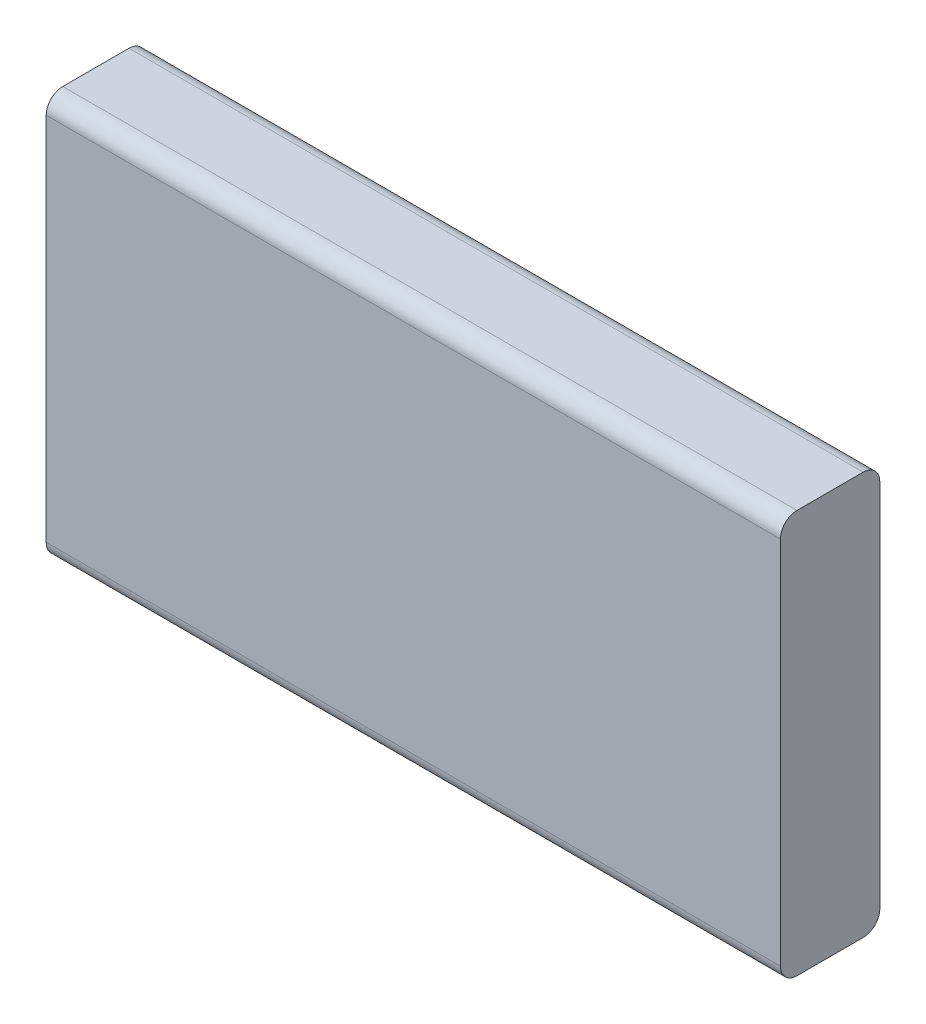
SolidWorks part; units mm, degrees
ref_plane "Plano frontal" through (0, 0, 0) normal (0, 0, 1) x (1, 0, 0)
ref_plane "Plano superior" through (0, 0, 0) normal (0, 1, 0) x (1, 0, 0)
ref_plane "Plano direito" through (0, 0, 0) normal (1, 0, 0) x (0, 0, -1)
sketch "Esboço1" plane through (0, 0, 0) normal (0, 0, 1) x (1, 0, 0)
  line L1 (-85.8282, 38.805) -> (47.1718, 38.805)
  line L2 (-85.8282, 38.805) -> (-85.8282, -34.195)
  line L3 (-85.8282, -34.195) -> (47.1718, -34.195)
  line L4 (47.1718, 38.805) -> (47.1718, -34.195)
  dimension "D1" = 73
  dimension "D2" = 133
extrude "Ressalto-extrusão1" add sketch "Esboço1" along normal blind 18
fillet "Filete1" radius 3 4 edges at (-19.3282, -34.195, 0) (-19.3282, -34.195, 18) (-19.3282, 38.805, 18) (-19.3282, 38.805, 0)
